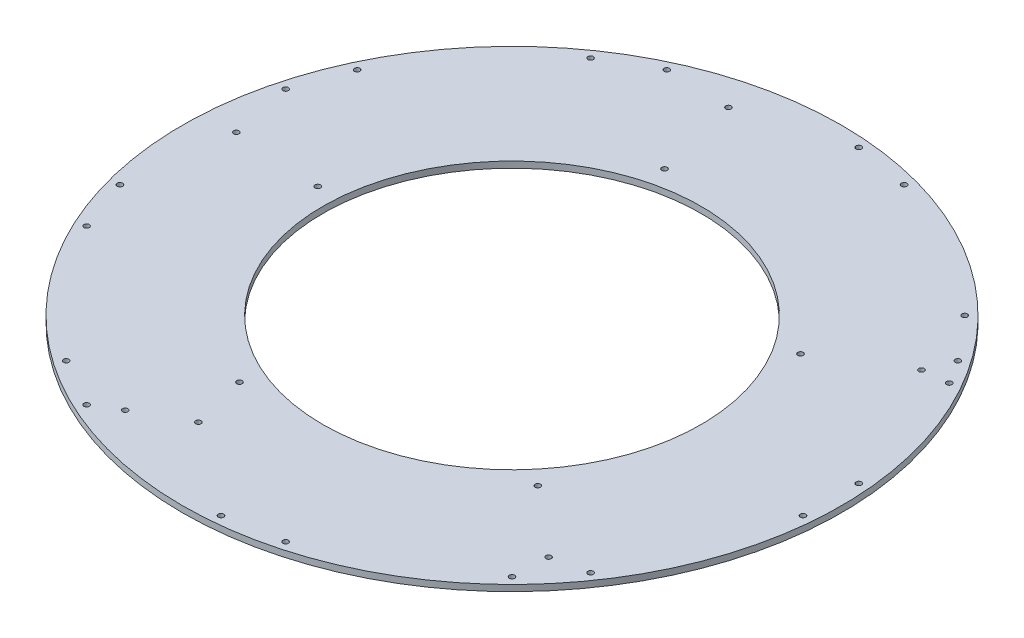
SolidWorks part; units mm, degrees
ref_plane "Front Plane" through (0, 0, 0) normal (0, 0, 1) x (1, 0, 0)
ref_plane "Top Plane" through (0, 0, 0) normal (0, 1, 0) x (1, 0, 0)
ref_plane "Right Plane" through (0, 0, 0) normal (1, 0, 0) x (0, 0, -1)
sketch "Sketch1" plane through (0, 0, 0) normal (0, 1, 0) x (1, 0, 0)
  circle A0 centre (0, 0) radius 309.88
  circle A1 centre (0, 0) radius 177.8
  dimension "D1" = 619.76
  dimension "D2" = 355.6
extrude "Boss-Extrude1" add sketch "Sketch1" along normal blind 5.842
ref_axis "Axis1" through (0, 6.6675, 0) along (0, -1, 0)
sketch "Sketch2" plane through (0, 5.842, 0) normal (0, 1, 0) x (1, 0, 0)
  line L0 (0, 0) -> (-309.88, 0) construction
  line L1 (0, 0) -> (-290.734, 77.9019) construction
  line L2 (0, 0) -> (-290.734, -77.9019) construction
  line L3 (-154.94, 41.516) -> (-154.94, 0) construction
  line L4 (-154.94, 0) -> (-154.94, -41.516) construction
  circle A1 centre (0, 0) radius 309.88 construction
  circle A2 centre (-290.734, -77.9019) radius 2.5527
  circle A3 centre (-290.734, 77.9019) radius 2.5527
  dimension "D2" = 300.99
  dimension "D3" = 5.1054
  dimension "D1" = 30
extrude "Cut-Extrude1" cut sketch "Sketch2" against normal through all
pattern_circular "CirPattern1" count 9 over 360 about axis through (0, 6.6675, 0) along (0, -1, 0) of "Cut-Extrude1"
sketch "Sketch3" plane through (0, 5.842, 0) normal (0, 1, 0) x (1, 0, 0)
  line L0 (0, 0) -> (-196.3705, 13.7316) construction
  line L1 (-196.3705, 13.7316) -> (-278.7194, 19.49) construction
  line L2 (0, 0) -> (-177.8, 0) construction
  circle A0 centre (-196.3705, 13.7316) radius 2.5527
  circle A1 centre (-278.7194, 19.49) radius 2.5527
  circle A2 centre (0, 0) radius 177.8 construction
  dimension "D1" = 5.1054
  dimension "D2" = 82.55
  dimension "D3" = 196.85
  dimension "D4" = 4
extrude "Holes_MountingFeet" cut sketch "Sketch3" against normal through all
pattern_circular "CirPattern_MountingFeet" count 5 over 360 about axis through (0, 6.6675, 0) along (0, -1, 0) of "Holes_MountingFeet"
sketch "Sketch4" plane through (0, 5.842, 0) normal (0, 1, 0) x (1, 0, 0)
  line L0 (0, 0) -> (309.88, 0) construction
  line L1 (260.665, 150.495) -> (0, 0) construction
  circle A0 centre (260.665, 150.495) radius 2.5527
  circle A1 centre (0, 0) radius 309.88 construction
  circle A2 centre (0, 0) radius 300.99 construction
  dimension "D2" = 5.1054
  dimension "D1" = 30
extrude "Hole_Wires" cut sketch "Sketch4" against normal through all
sketch "Sketch5" plane through (0, 5.842, 0) normal (0, 1, 0) x (1, 0, 0)
  line L0 (-73.7413, -182.5161) -> (-104.6651, -259.0552) construction
  line L1 (-60.4787, -234.4457) -> (-89.9168, -222.5519) construction
  circle A0 centre (-60.4787, -234.4457) radius 2.5527
  dimension "D1" = 5.1054
  dimension "D2" = 43.18
  dimension "D3" = 31.75
extrude "Cut-Extrude2" cut sketch "Sketch5" against normal through all
